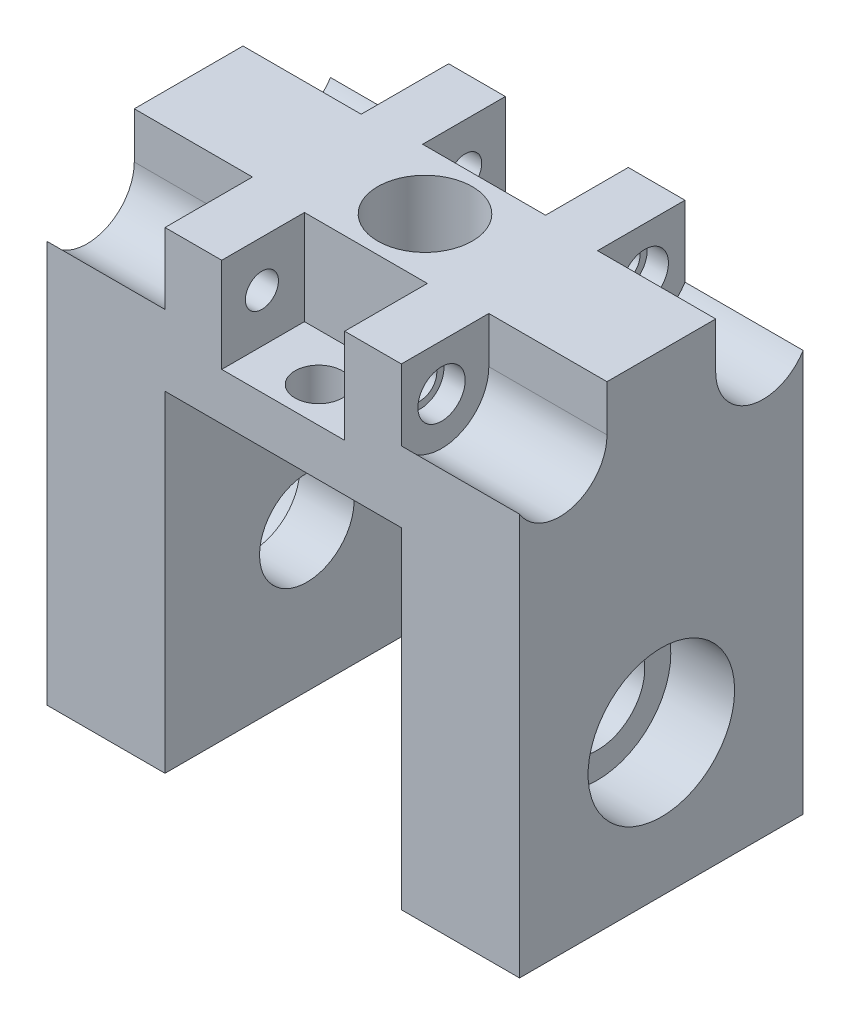
SolidWorks part; units mm, degrees
note: The reader was unsure of these and kept them because the rebuilt part matched: shared geometry of "草图2<3>", "草图6<3>", "草图6<4>", "草图7<3>", "草图7<4>", "草图7<5>", "草图7<6>", "草图7<7>", "草图7<8>".
ref_plane "前视基准面" through (0, 0, 0) normal (0, 0, 1) x (1, 0, 0)
ref_plane "上视基准面" through (0, 0, 0) normal (0, 1, 0) x (1, 0, 0)
ref_plane "右视基准面" through (0, 0, 0) normal (1, 0, 0) x (0, 0, -1)
other "Configuration Table"
sketch "草图1" plane through (0, 0, 0) normal (0, 1, 0) x (1, 0, 0)
  line L1 (0, 0) -> (10, 0)
  line L2 (0, 0) -> (0, -12)
  line L3 (0, -12) -> (10, -12)
  line L4 (10, 0) -> (10, -12)
  dimension "D4" = 10
  dimension "D11" = 12
extrude "凸台-拉伸1" add sketch "草图1" along normal blind 6
sketch "草图2" plane through (0, 6, 0) normal (0, 1, 0) x (1, 0, 0)
  circle A0 centre (5, -1.5) radius 2
  circle A1 centre (5, -10.5) radius 2
  circle A2 centre (5, -1.5) radius 1
  circle A3 centre (5, -10.5) radius 1
  dimension "D1" = 2
  dimension "D2" = 4
extrude "切除-拉伸1" cut sketch "草图2" against normal through all contours A2 | A3
extrude "切除-拉伸2" cut sketch "草图2<3>" against normal offset from surface (4 mm away) 2 contours A0 | A1 up to face at (5, 0, 2.5)
sketch "草图2<3>" plane through (0, 6, 0) normal (0, 1, 0) x (1, 0, 0) same geometry as "草图2"
sketch "草图3" plane through (0, 6, 0) normal (0, 1, 0) x (1, 0, 0)
  line L0 (10, 0) -> (0, -12)
  circle A0 centre (5, -6) radius 2
  dimension "D1" = 4
extrude "切除-拉伸3" cut sketch "草图3" against normal through all contours A0
sketch "草图4" plane through (0, 6, 0) normal (0, 1, 0) x (1, 0, 0)
  line L0 (10, 0) -> (6.3229, 0) construction
  line L1 (7.6, 0) -> (2.4, 0)
  line L2 (7.6, 0) -> (7.6, -3.5)
  line L3 (7.6, -3.5) -> (2.4, -3.5)
  line L4 (2.4, 0) -> (2.4, -3.5)
  line L5 (6.3229, -12) -> (10, -12) construction
  line L6 (7.6, -12) -> (2.4, -12)
  line L7 (7.6, -12) -> (7.6, -8.5)
  line L8 (7.6, -8.5) -> (2.4, -8.5)
  line L9 (2.4, -12) -> (2.4, -8.5)
  line L10 (10, -12) -> (10, 0) construction
  line L11 (0, 0) -> (0, -12) construction
  arc A0 (3.6771, 0) -> (6.3229, 0) centre (5, -1.5) ccw construction
  arc A1 (6.3229, -12) -> (3.6771, -12) centre (5, -10.5) ccw construction
  dimension "D1" = 2.4
  dimension "D2" = 2.4
extrude "切除-拉伸4" cut sketch "草图4" against normal up to surface (4 mm away) contours L4 L3 L2 L1 | L9 L8 L7 L6 up to face at (5, 2, 2.5)
sketch "草图6" plane through (0, 0, 0) normal (-1, 0, 0) x (0, 0, 1)
  circle A0 centre (1.7, 4.05) radius 1
  circle A1 centre (10.3, 4.05) radius 1
  circle A2 centre (1.7, 4.05) radius 0.7
  circle A3 centre (10.3, 4.05) radius 0.7
  dimension "D1" = 2
  dimension "D2" = 1.4
extrude "切除-拉伸5" cut sketch "草图6" against normal through all contours A2 | A3
extrude "切除-拉伸6" cut sketch "草图6<3>" against normal offset from surface (0.9 mm away) 1.5 contours A0 | A1 up to face at (2.4, 4.05, 2.4)
sketch "草图6<3>" plane through (0, 0, 0) normal (-1, 0, 0) x (0, 0, 1) same geometry as "草图6"
extrude "切除-拉伸7" cut sketch "草图6<4>" along normal offset from surface (0.9 mm away) 1.5 from surface at -10 contours A0 | A1 up to face at (7.6, 4.05, 2.4) starting at face at (10, 4.05, 2.4)
sketch "草图6<4>" plane through (0, 0, 0) normal (-1, 0, 0) x (0, 0, 1) same geometry as "草图6"
sketch "草图7" plane through (10, 0, 0) normal (1, 0, 0) x (0, 0, -1)
  line L0 (0, 6) -> (0, 0) construction
  line L1 (-12, 6) -> (0, 6)
  line L2 (-12, 6) -> (-12, -14)
  line L3 (-12, -14) -> (0, -14)
  line L4 (0, 6) -> (0, -14)
  line L5 (-8.3, 4.05) -> (-8.3, 6)
  line L7 (-3.7, 4.05) -> (-3.7, 6)
  circle A0 centre (-10.3, 4.05) radius 2
  circle A1 centre (-1.7, 4.05) radius 2
  circle A2 centre (-10.3, 4.05) radius 0.7 construction
  circle A3 centre (-1.7, 4.05) radius 0.7 construction
  circle A4 centre (-6, -8) radius 3.1
  circle A5 centre (-6, -8) radius 2
  point P23 (-4.1284, -4.6198)
  point P24 (-6, -14)
  circle M5 centre (-1.7, 4.05) radius 1
  circle M6 centre (-10.3, 4.05) radius 1
  line M8 (0, 0) -> (0, 6)
  line M9 (0, 6) -> (-12, 6)
  line M10 (-12, 6) -> (-12, 0)
  dimension "D2" = 4
  dimension "D3" = 4
  dimension "D4" = 6.2
  dimension "D1" = 20
  dimension "D5" = 6
extrude "凸台-拉伸2" add sketch "草图7" along normal blind 5 contours L2 L3 L4 L1
extrude "切除-拉伸8" cut sketch "草图7<3>" against normal blind 5 from surface at 5 contours A0 M9 M10 | A1 M8 M9 | A0 L5 L1 | A1 L7 M9 starting at face at (15, -4, 6)
sketch "草图7<3>" plane through (10, 0, 0) normal (1, 0, 0) x (0, 0, -1) same geometry as "草图7"
extrude "凸台-拉伸3" add sketch "草图7<4>" against normal blind 5 from surface at -10 contours L4 L3 L2 L1 starting at face at (0, 4.05, 2.7)
sketch "草图7<4>" plane through (10, 0, 0) normal (1, 0, 0) x (0, 0, -1) same geometry as "草图7"
extrude "切除-拉伸9" cut sketch "草图7<5>" along normal blind 5 from surface at -15 contours A0 L2 M9 M6 | A0 L5 L1 | A0 L1 M10 | L4 A1 L1 M5 | A1 L7 M9 | A1 M8 M9 | M6 | M5 starting at face at (-5, -4, 6)
sketch "草图7<5>" plane through (10, 0, 0) normal (1, 0, 0) x (0, 0, -1) same geometry as "草图7"
extrude "切除-拉伸10" cut sketch "草图7<6>" against normal through all both and the other way through all contours A5
sketch "草图7<6>" plane through (10, 0, 0) normal (1, 0, 0) x (0, 0, -1) same geometry as "草图7"
extrude "切除-拉伸11" cut sketch "草图7<7>" against normal blind 2.7 from surface at 5 contours A4 starting at face at (15, -8, 4)
sketch "草图7<7>" plane through (10, 0, 0) normal (1, 0, 0) x (0, 0, -1) same geometry as "草图7"
extrude "切除-拉伸12" cut sketch "草图7<8>" along normal blind 2.7 from surface at -15 contours A4 starting at face at (-5, -8, 4)
sketch "草图7<8>" plane through (10, 0, 0) normal (1, 0, 0) x (0, 0, -1) same geometry as "草图7"
